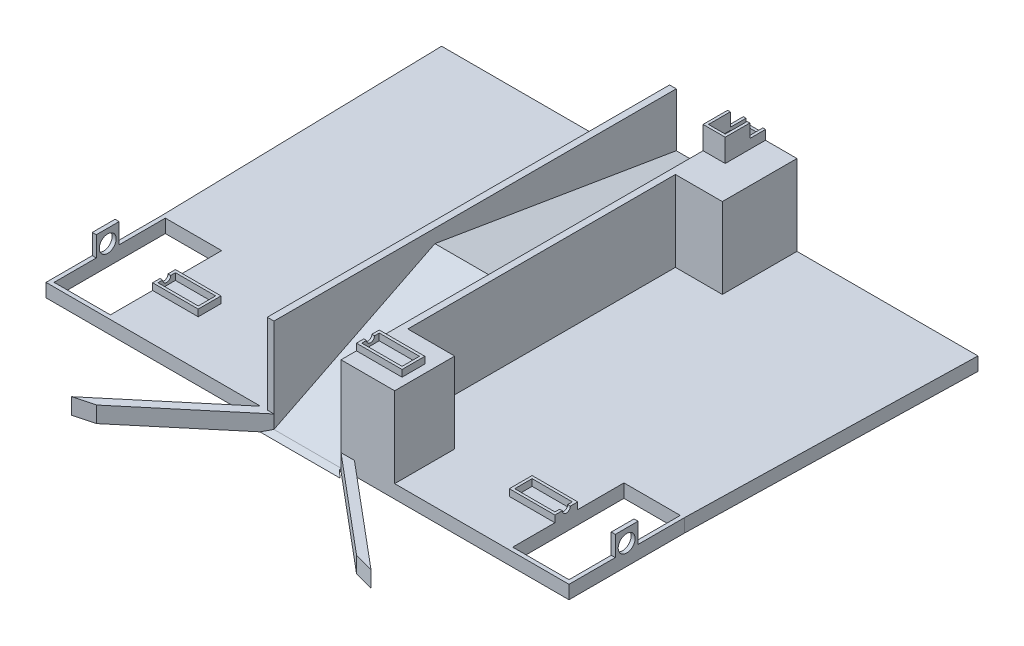
SolidWorks part; units mm, degrees
ref_plane "Front Plane" through (0, 0, 0) normal (0, 0, 1) x (1, 0, 0)
ref_plane "Top Plane" through (0, 0, 0) normal (0, 1, 0) x (1, 0, 0)
ref_plane "Right Plane" through (0, 0, 0) normal (1, 0, 0) x (0, 0, -1)
sketch "Sketch1" plane through (0, 0, 0) normal (0, 1, 0) x (1, 0, 0)
  line L1 (-100.4558, 255.2091) -> (299.5442, 255.2091)
  line L2 (-100.4558, 255.2091) -> (-95.4558, 41.2091)
  line L3 (-50.4558, -44.7909) -> (249.5442, -44.7909)
  line L5 (-95.4558, 41.2091) -> (-50.4558, 41.2091)
  line L8 (-50.4558, 41.2091) -> (-50.4558, -44.7909)
  line L23 (99.5442, 255.2091) -> (99.5442, -44.7909) construction
  line L32 (294.5442, 41.2091) -> (249.5442, 41.2091)
  line L33 (299.5442, 255.2091) -> (294.5442, 41.2091)
  line L34 (249.5442, 41.2091) -> (249.5442, -44.7909)
  point P32 (199.0884, -22.3492)
  dimension "D3" = 200
  dimension "D4" = 300
  dimension "D2" = 86
  dimension "D11" = 45
  dimension "D12" = 150
extrude "Boss-Extrude3" add sketch "Sketch1" along normal blind 10
sketch "Sketch2" plane through (0, 10, 0) normal (0, 1, 0) x (1, 0, 0)
  line L0 (-50.4558, 41.2091) -> (-50.4558, -44.7909) construction
  line L1 (-50.4558, 6.7091) -> (-16.4558, 6.7091)
  line L3 (-50.4558, 6.7091) -> (-50.4558, -10.2909)
  line L4 (-50.4558, -10.2909) -> (-16.4558, -10.2909)
  line L5 (-16.4558, 6.7091) -> (-16.4558, -10.2909)
  line L6 (-13, 6.7091) -> (-33.4558, -10.2909) construction
  line L7 (-48.4558, 4.7091) -> (-18.4558, 4.7091)
  line L8 (-48.4558, 4.7091) -> (-48.4558, -8.2909)
  line L9 (-48.4558, -8.2909) -> (-18.4558, -8.2909)
  line L10 (-18.4558, 4.7091) -> (-18.4558, -8.2909)
  line L11 (-16.4558, -1.7909) -> (-50.4558, -1.7909) construction
  line L12 (-50.4558, -44.7909) -> (249.5442, -44.7909) construction
  line L13 (99.5442, 255.2091) -> (99.5442, -44.7909) construction
  line L14 (299.5442, 255.2091) -> (-100.4558, 255.2091) construction
  line L15 (215.5442, -1.7909) -> (249.5442, -1.7909) construction
  line L16 (212.0884, 6.7091) -> (232.5442, -10.2909) construction
  line L17 (217.5442, 4.7091) -> (217.5442, -8.2909)
  line L18 (247.5442, -8.2909) -> (217.5442, -8.2909)
  line L19 (247.5442, 4.7091) -> (247.5442, -8.2909)
  line L20 (247.5442, 4.7091) -> (217.5442, 4.7091)
  line L21 (215.5442, 6.7091) -> (215.5442, -10.2909)
  line L22 (249.5442, -10.2909) -> (215.5442, -10.2909)
  line L23 (249.5442, 6.7091) -> (249.5442, -10.2909)
  line L24 (249.5442, 6.7091) -> (215.5442, 6.7091)
  dimension "D1" = 2
  dimension "D2" = 2
  dimension "D3" = 2
  dimension "D4" = 2
  dimension "D5" = 30
  dimension "D6" = 13
  dimension "D7" = 43
extrude "Boss-Extrude4" add sketch "Sketch2" along normal blind 5
sketch "Sketch3" plane through (0, 10, 0) normal (0, 1, 0) x (1, 0, 0)
  line L0 (99.5442, 255.2091) -> (99.5442, -44.7909) construction
  line L1 (299.5442, 255.2091) -> (-100.4558, 255.2091) construction
  line L2 (-50.4558, -44.7909) -> (249.5442, -44.7909) construction
  line L3 (74.5442, -44.7909) -> (74.5442, 75.2091)
  line L4 (74.5442, 75.2091) -> (124.5442, 75.2091)
  line L5 (124.5442, 75.2091) -> (124.5442, -44.7909)
  line L22 (215.5442, -10.2909) -> (215.5442, 6.7091)
  line L23 (215.5442, 6.7091) -> (249.5442, 6.7091)
  line L24 (249.5442, 6.7091) -> (249.5442, 41.2091)
  line L25 (249.5442, 41.2091) -> (294.5442, 41.2091)
  line L26 (294.5442, 41.2091) -> (299.5442, 255.2091)
  line L27 (299.5442, 255.2091) -> (-100.4558, 255.2091)
  line L28 (-100.4558, 255.2091) -> (-95.4558, 41.2091)
  line L29 (-95.4558, 41.2091) -> (-50.4558, 41.2091)
  line L30 (-50.4558, 41.2091) -> (-50.4558, 6.7091)
  line L31 (-50.4558, 6.7091) -> (-16.4558, 6.7091)
  line L32 (-16.4558, 6.7091) -> (-16.4558, -10.2909)
  line L33 (-16.4558, -10.2909) -> (-50.4558, -10.2909)
  line L34 (-50.4558, -10.2909) -> (-50.4558, -44.7909)
  line L35 (-50.4558, -44.7909) -> (249.5442, -44.7909)
  line L36 (249.5442, -44.7909) -> (249.5442, -10.2909)
  line L37 (249.5442, -10.2909) -> (215.5442, -10.2909)
  line L51 (74.5442, -44.7909) -> (124.5442, -44.7909)
  dimension "D1" = 50
  dimension "D2" = 25
  dimension "D3" = 120
extrude "Boss-Extrude5" add sketch "Sketch3" along normal blind 50
sketch "Sketch4" plane through (124.5442, 0, 0) normal (1, 0, 0) x (0, 0, -1)
  line L2 (-44.7909, 60) -> (75.2091, 60)
  line L3 (75.2091, 60) -> (-44.7909, 0)
  line L4 (-44.7909, 60) -> (-44.7909, 0)
extrude "Cut-Extrude2" cut sketch "Sketch4" against normal up to vertex (50 mm away) up to point (74.5442, 60, 44.7909)
sketch "Sketch5" plane through (0, 10, 0) normal (0, 1, 0) x (1, 0, 0)
  line L0 (74.5442, 75.2091) -> (74.5442, 255.2091)
  line L1 (299.5442, 255.2091) -> (-100.4558, 255.2091) construction
  line L2 (74.5442, 255.2091) -> (124.5442, 255.2091)
  line L3 (124.5442, 255.2091) -> (124.5442, 75.2091)
  line L4 (74.5442, 75.2091) -> (124.5442, 75.2091)
  line L5 (74.5442, 75.2091) -> (74.5442, -24.7909) construction
extrude "Boss-Extrude6" add sketch "Sketch5" along normal blind 50
sketch "Sketch6" plane through (124.5442, 0, 0) normal (1, 0, 0) x (0, 0, -1)
  line L2 (75.2091, 60) -> (255.2091, 60)
  line L3 (255.2091, 60) -> (255.2091, 30)
  line L4 (255.2091, 60) -> (255.2091, 10) construction
  line L5 (255.2091, 30) -> (75.2091, 60)
  dimension "D1" = 30
extrude "Cut-Extrude3" cut sketch "Sketch6" against normal through all contours L2 L3 L5
sketch "Sketch7" plane through (0, 0, 0) normal (0, 1, 0) x (1, 0, 0)
  line L0 (69.5442, 255.2091) -> (69.5442, -44.7909)
  line L1 (74.5442, 255.2091) -> (-100.4558, 255.2091) construction
  line L2 (-50.4558, -44.7909) -> (74.5442, -44.7909) construction
  line L3 (69.5442, -44.7909) -> (74.5442, -44.7909)
  line L4 (74.5442, -44.7909) -> (74.5442, 255.2091)
  line L5 (74.5442, 255.2091) -> (74.5442, -24.7909) construction
  line L6 (74.5442, 255.2091) -> (124.5442, 255.2091) construction
  line L7 (74.5442, 255.2091) -> (69.5442, 255.2091)
  line L8 (124.5442, 255.2091) -> (129.5442, 255.2091)
  line L9 (299.5442, 255.2091) -> (124.5442, 255.2091) construction
  line L10 (129.5442, 255.2091) -> (129.5442, -44.7909)
  line L11 (124.5442, -44.7909) -> (249.5442, -44.7909) construction
  line L12 (129.5442, -44.7909) -> (124.5442, -44.7909)
  line L13 (124.5442, -44.7909) -> (124.5442, 255.2091)
  line L14 (129.5442, -44.7909) -> (164.5442, -44.7909)
  line L15 (124.5442, -44.7909) -> (249.5442, -44.7909) construction
  line L16 (164.5442, -44.7909) -> (164.5442, 0)
  line L17 (164.5442, 0) -> (129.5442, 0)
  dimension "D1" = 5
  dimension "D2" = 5
  dimension "D3" = 35
extrude "Boss-Extrude7" add sketch "Sketch7" along normal blind 70 contours L16 L17 L10 L14 | L7 L0 L3 L4 | L13 L8 L10 L12 region at (147.0442, 0, 22.3954)
sketch "Sketch9" plane through (0, 70, 0) normal (0, 1, 0) x (1, 0, 0)
  line L0 (124.5442, -44.7909) -> (124.5442, 75.2091) construction
  line L1 (124.5442, -16.2909) -> (158.5442, -16.2909)
  line L2 (124.5442, -16.2909) -> (124.5442, -33.2909)
  line L3 (124.5442, -33.2909) -> (158.5442, -33.2909)
  line L4 (158.5442, -16.2909) -> (158.5442, -33.2909)
  line L5 (158.5442, -24.7909) -> (124.5442, -24.7909) construction
  line L6 (126.5442, -18.2909) -> (156.5442, -18.2909)
  line L7 (126.5442, -18.2909) -> (126.5442, -31.2909)
  line L8 (126.5442, -31.2909) -> (156.5442, -31.2909)
  line L9 (156.5442, -18.2909) -> (156.5442, -31.2909)
  line L10 (141.5442, -16.2909) -> (141.5442, -35.4954) construction
  line L11 (164.5442, -44.7909) -> (124.5442, -44.7909) construction
  dimension "D1" = 2
  dimension "D2" = 2
  dimension "D3" = 2
  dimension "D4" = 2
  dimension "D5" = 30
  dimension "D6" = 13
  dimension "D7" = 20
extrude "Boss-Extrude8" add sketch "Sketch9" along normal blind 5 contours L2 L1 L4 L3 | L7 L6 L9 L8
sketch "Sketch10" plane through (129.5442, 0, 0) normal (1, 0, 0) x (0, 0, -1)
  line L0 (199.5615, 70) -> (199.5615, 10)
  line L1 (255.2091, 70) -> (0, 70) construction
  line L2 (0, 10) -> (255.2091, 10) construction
  line L3 (199.5615, 10) -> (255.2091, 10)
  line L4 (255.2091, 10) -> (255.2091, 70)
  line L5 (255.2091, 70) -> (199.5615, 70)
extrude "Boss-Extrude9" add sketch "Sketch10" along normal blind 35
sketch "Sketch13" plane through (0, 70, 0) normal (0, 1, 0) x (1, 0, 0)
  line L0 (141.0442, 225.2091) -> (124.5442, 225.2091)
  line L2 (124.5442, 225.2091) -> (124.5442, 255.2091)
  line L3 (124.5442, 255.2091) -> (141.0442, 255.2091)
  line L4 (141.0442, 255.2091) -> (141.0442, 225.2091)
  line L5 (139.0442, 227.2091) -> (126.5442, 227.2091)
  line L6 (126.5442, 227.2091) -> (126.5442, 253.2091)
  line L7 (126.5442, 253.2091) -> (139.0442, 253.2091)
  line L8 (139.0442, 253.2091) -> (139.0442, 227.2091)
  line L15 (124.5442, 255.2091) -> (164.5442, 255.2091) construction
  point P2 (126.7166, 255.2091)
  point P8 (141.5391, 254.8671)
  point P12 (135.5412, 253.2055)
  point P13 (137.5482, 231.331)
  point P14 (0, 0)
  point P16 (141.0442, 231.7091)
  dimension "D2" = 16.5
  dimension "D3" = 30
  dimension "D4" = 2
  dimension "D5" = 2
  dimension "D6" = 2
  dimension "D7" = 2
extrude "Boss-Extrude11" add sketch "Sketch13" along normal blind 7
sketch "Sketch14" plane through (0, 0, 0) normal (0, -1, 0) x (1, 0, 0)
  line L0 (294.5442, -41.2091) -> (299.5442, -255.2091) construction
  line L1 (299.5442, -255.2091) -> (-100.4558, -255.2091) construction
  circle A0 centre (284.1896, -240.2091) radius 8
  dimension "D1" = 15
  dimension "D2" = 15
sketch "Sketch16" plane through (0, 0, 0) normal (0, -1, 0) x (1, 0, 0)
  line L0 (-100.4558, -255.2091) -> (-95.4558, -41.2091) construction
  line L1 (299.5442, -255.2091) -> (-100.4558, -255.2091) construction
  circle A0 centre (-85.1012, -240.2091) radius 8
  dimension "D1" = 15
  dimension "D2" = 15
sketch "Sketch19" plane through (0, 0, 44.7909) normal (0, 0, 1) x (1, 0, 0)
  line L0 (-50.4558, 10) -> (69.5442, 10) construction
  line L1 (74.5442, 0) -> (64.5442, 0)
  line L2 (74.5442, 0) -> (74.5442, 10)
  line L3 (74.5442, 10) -> (64.5442, 10)
  line L4 (64.5442, 0) -> (64.5442, 10)
  line L6 (124.5442, 0) -> (134.5442, 0)
  line L7 (124.5442, 0) -> (124.5442, 10)
  line L8 (124.5442, 10) -> (134.5442, 10)
  line L9 (134.5442, 0) -> (134.5442, 10)
  point P12 (0, 0)
  dimension "D1" = 10
  dimension "D2" = 10
  dimension "D3" = 10
sketch "Sketch20" plane through (0, 0, 0) normal (0, 1, 0) x (1, 0, 0)
  line L0 (64.5442, -44.7909) -> (-12.0602, -109.0696)
  line L1 (74.5442, -44.7909) -> (64.5442, -44.7909) construction
  line L2 (74.5442, -44.7909) -> (2.6312, -105.1331)
  line L3 (74.5442, -44.7909) -> (64.5442, -44.7909) construction
  line L4 (-50.4558, -44.7909) -> (69.5442, -44.7909) construction
  line L5 (124.5442, -44.7909) -> (196.4572, -105.1331)
  line L6 (134.5442, -44.7909) -> (211.1486, -109.0696)
  line L7 (124.5442, -44.7909) -> (134.5442, -44.7909) construction
  line L8 (164.5442, -44.7909) -> (124.5442, -44.7909) construction
  line L9 (196.4572, -105.1331) -> (211.1486, -109.0696)
  line L10 (2.6312, -105.1331) -> (-12.0602, -109.0696)
  line L11 (64.5442, -44.7909) -> (74.5442, -44.7909)
  line L12 (124.5442, -44.7909) -> (134.5442, -44.7909)
  dimension "D1" = 40
  dimension "D2" = 40
  dimension "D3" = 25
  dimension "D4" = 25
  dimension "D5" = 100
  dimension "D6" = 100
  dimension "D7" = 10
  dimension "D8" = 10
extrude "Boss-Extrude16" add sketch "Sketch20" along normal blind 10 and the other way blind 2
sketch "Sketch21" plane through (0, 0, 0) normal (0, -1, 0) x (1, 0, 0)
  line L0 (74.5442, 44.7909) -> (124.5442, 44.7909) construction
  line L1 (74.5442, 44.6775) -> (124.5442, 44.6775)
  line L2 (74.5442, 44.6775) -> (74.5442, 14.7909)
  line L3 (74.5442, 14.7909) -> (124.5442, 14.7909)
  line L4 (124.5442, 44.6775) -> (124.5442, 14.7909)
  dimension "D1" = 50
  dimension "D2" = 30
extrude "Boss-Extrude19" add sketch "Sketch21" along normal blind 2
sketch "Sketch23" plane through (124.5442, 0, 0) normal (1, 0, 0) x (0, 0, -1)
  line L0 (-44.7909, 0) -> (-49.5909, -2)
  line L1 (-109.0696, -2) -> (-44.7909, -2) construction
  line L2 (-49.5909, -2) -> (-44.6775, -2)
  line L3 (-44.6775, -2) -> (-49.5909, -2)
  line L5 (-44.7909, 0) -> (-44.6775, -2)
  point P5 (-44.7909, -25)
  dimension "D1" = 22.62
sketch "Sketch24" plane through (0, 0, 44.7909) normal (0, 0, -1) x (-1, 0, 0)
  line L1 (-74.5442, 0) -> (-64.5442, 0)
  line L2 (-74.5442, 0) -> (-74.5442, -2)
  line L3 (-74.5442, -2) -> (-64.5442, -2)
  line L4 (-64.5442, 0) -> (-64.5442, -2)
  line L5 (-134.5442, 0) -> (-124.5442, 0)
  line L6 (-134.5442, 0) -> (-134.5442, -2)
  line L7 (-134.5442, -2) -> (-124.5442, -2)
  line L8 (-124.5442, 0) -> (-124.5442, -2)
extrude "Boss-Extrude20" add sketch "Sketch24" along normal blind 30
extrude "Boss-Extrude23" add sketch "Sketch23" along normal offset from surface 1 and the other way up to surface separate body contours L5 L0 L2 region at (124.5442, -1.3333, 46.3531) up to face at (153.3094, 3.2, 68.9277) other way up to face at (45.779, 3.2, 68.9277)
sketch "Sketch28" plane through (0, 0, -41.2091) normal (0, 0, 1) x (1, 0, 0)
  line L0 (-95.4558, 0) -> (-50.4558, 0) construction
  line L1 (-95.4558, 10) -> (-92.4558, 10)
  line L2 (-95.4558, 10) -> (-95.4558, 0)
  line L3 (-95.4558, 0) -> (-92.4558, 0)
  line L4 (-92.4558, 10) -> (-92.4558, 0)
  dimension "D1" = 3
extrude "Boss-Extrude24" add sketch "Sketch28" along normal up to vertex (86 mm away) up to point (-50.4558, 0, 44.7909)
sketch "Sketch29" plane through (-50.4558, 0, 0) normal (-1, 0, 0) x (0, 0, 1)
  line L0 (14.7909, 0) -> (44.7909, 0) construction
  line L1 (44.7909, 10) -> (41.7909, 10)
  line L2 (44.7909, 10) -> (44.7909, 0)
  line L3 (44.7909, 0) -> (41.7909, 0)
  line L4 (41.7909, 10) -> (41.7909, 0)
  point P7 (0, 0)
  dimension "D1" = 3
extrude "Boss-Extrude25" add sketch "Sketch29" along normal up to next
sketch "Sketch30" plane through (0, 0, -41.2091) normal (0, 0, 1) x (1, 0, 0)
  line L0 (249.5442, 0) -> (294.5442, 0) construction
  line L1 (294.5442, 10) -> (291.5442, 10)
  line L2 (294.5442, 10) -> (294.5442, 0)
  line L3 (294.5442, 0) -> (291.5442, 0)
  line L4 (291.5442, 10) -> (291.5442, 0)
  dimension "D1" = 3
extrude "Boss-Extrude26" add sketch "Sketch30" along normal up to vertex (86 mm away) up to point (249.5442, 0, 44.7909)
sketch "Sketch31" plane through (249.5442, 0, 0) normal (1, 0, 0) x (0, 0, -1)
  line L0 (-14.7909, 0) -> (-44.7909, 0) construction
  line L1 (-44.7909, 10) -> (-41.7909, 10)
  line L2 (-44.7909, 10) -> (-44.7909, 0)
  line L3 (-44.7909, 0) -> (-41.7909, 0)
  line L4 (-41.7909, 10) -> (-41.7909, 0)
  dimension "D1" = 3
extrude "Boss-Extrude27" add sketch "Sketch31" along normal up to next
sketch "Sketch32" plane through (0, 70, 0) normal (0, 1, 0) x (1, 0, 0)
  line L0 (126.5442, 253.2091) -> (126.5442, 227.2091) construction
  line L1 (139.0442, 227.2091) -> (126.5442, 227.2091)
  line L2 (139.0442, 227.2091) -> (139.0442, 243.5091)
  line L3 (139.0442, 243.5091) -> (126.5442, 243.5091)
  line L4 (126.5442, 227.2091) -> (126.5442, 243.5091)
  dimension "D1" = 16.3
extrude "Boss-Extrude28" add sketch "Sketch32" along normal blind 5
sketch "Sketch34" plane through (0, 77, 0) normal (0, 1, 0) x (1, 0, 0)
  line L0 (126.5442, 243.5091) -> (124.5442, 243.5091)
  line L1 (124.5442, 255.2091) -> (124.5442, 225.2091) construction
  line L2 (124.5442, 243.5091) -> (124.5442, 225.2091)
  line L3 (124.5442, 225.2091) -> (141.0442, 225.2091)
  line L4 (124.5442, 225.2091) -> (141.0442, 225.2091) construction
  line L5 (141.0442, 225.2091) -> (141.0442, 243.5091)
  line L6 (141.0442, 225.2091) -> (141.0442, 255.2091) construction
  line L7 (141.0442, 243.5091) -> (139.0442, 243.5091)
  line L8 (139.0442, 243.5091) -> (139.0442, 227.2091)
  line L9 (139.0442, 227.2091) -> (126.5442, 227.2091)
  line L10 (126.5442, 227.2091) -> (126.5442, 243.5091)
  point P5 (141.0442, 231.7091)
extrude "Boss-Extrude31" add sketch "Sketch34" along normal blind 10
sketch "Sketch35" plane through (0, 0, -255.2091) normal (0, 0, -1) x (-1, 0, 0)
  line L0 (-139.0442, 77) -> (-139.0442, 74)
  line L1 (-141.0442, 77) -> (-124.5442, 77) construction
  line L2 (-139.0442, 74) -> (-126.5442, 74)
  line L3 (-126.5442, 74) -> (-126.5442, 77)
  line L4 (-141.0442, 77) -> (-141.0442, 70) construction
  line L5 (-124.5442, 77) -> (-124.5442, 30) construction
  line L6 (-139.0442, 77) -> (-126.5442, 77)
  dimension "D1" = 2
  dimension "D2" = 2
  dimension "D3" = 3
extrude "Cut-Extrude4" cut sketch "Sketch35" against normal up to next (2 mm away)
sketch "Sketch36" plane through (249.5442, 0, 0) normal (1, 0, 0) x (0, 0, -1)
  line L0 (-10.2909, 15) -> (6.7091, 15) construction
  arc A0 (1.2091, 15) -> (-4.7909, 15) centre (-1.7909, 15) cw
  point P5 (0, 15)
  dimension "D1" = 3
extrude "Cut-Extrude5" cut sketch "Sketch36" against normal blind 2 and the other way through all flip side to cut
sketch "Sketch37" plane through (-50.4558, 0, 0) normal (-1, 0, 0) x (0, 0, 1)
  line L0 (-6.7091, 15) -> (10.2909, 15) construction
  arc A0 (-1.2091, 15) -> (4.7909, 15) centre (1.7909, 15) ccw
  point P5 (0, 15)
  dimension "D1" = 3
extrude "Cut-Extrude6" cut sketch "Sketch37" against normal blind 2 and the other way through all
sketch "Sketch38" plane through (124.5442, 0, 0) normal (-1, 0, 0) x (0, 0, 1)
  line L0 (16.2909, 75) -> (33.2909, 75) construction
  line L1 (21.7909, 75) -> (27.7909, 75)
  arc A0 (27.7909, 75) -> (21.7909, 75) centre (24.7909, 75) cw
  dimension "D1" = 3
extrude "Cut-Extrude9" cut sketch "Sketch38" against normal blind 2
sketch "Sketch39" plane through (0, 10, 0) normal (0, 1, 0) x (1, 0, 0)
  line L0 (291.5442, 6.7091) -> (294.5442, 6.7091)
  line L1 (291.5442, -41.7909) -> (291.5442, 41.2091) construction
  line L2 (294.5442, 6.7091) -> (294.5442, -10.2909)
  line L3 (294.5442, -10.2909) -> (291.5442, -10.2909)
  line L4 (291.5442, 6.7091) -> (291.5442, -10.2909)
  line L5 (249.5442, 6.7091) -> (291.5442, 6.7091) construction
  line L6 (249.5442, -10.2909) -> (291.5442, -10.2909) construction
  line L7 (294.5442, -44.7909) -> (294.5442, 41.2091) construction
  point P9 (0, 0)
  point P11 (0, 0)
extrude "Boss-Extrude32" add sketch "Sketch39" along normal blind 15
sketch "Sketch40" plane through (294.5442, 0, 0) normal (1, 0, 0) x (0, 0, -1)
  line L0 (-1.7909, 25) -> (-1.7909, 0) construction
  line L1 (-10.2909, 25) -> (6.7091, 25) construction
  line L2 (-44.7909, 0) -> (41.2091, 0) construction
  line L3 (-10.2909, 15) -> (6.7091, 15) construction
  line L4 (-10.2909, 25) -> (-10.2909, 10) construction
  line L5 (6.7091, 25) -> (6.7091, 10) construction
  line L6 (0, 10) -> (-44.7909, 10) construction
  circle A0 centre (-1.7909, 15) radius 6.3
  dimension "D2" = 12.6
  dimension "D1" = 5
extrude "Cut-Extrude10" cut sketch "Sketch40" against normal up to next (3 mm away)
sketch "Sketch41" plane through (0, 10, 0) normal (0, 1, 0) x (1, 0, 0)
  line L0 (-95.4558, 6.7091) -> (-92.4558, 6.7091)
  line L1 (-95.4558, -44.7909) -> (-95.4558, 41.2091) construction
  line L2 (-92.4558, -41.7909) -> (-92.4558, 41.2091) construction
  line L3 (-92.4558, 6.7091) -> (-92.4558, -10.2909)
  line L4 (-92.4558, -10.2909) -> (-95.4558, -10.2909)
  line L5 (-95.4558, -10.2909) -> (-95.4558, 6.7091)
  line L6 (-92.4558, 6.7091) -> (-50.4558, 6.7091) construction
  line L7 (-92.4558, -10.2909) -> (-50.4558, -10.2909) construction
extrude "Boss-Extrude33" add sketch "Sketch41" along normal blind 15
sketch "Sketch42" plane through (-95.4558, 0, 0) normal (-1, 0, 0) x (0, 0, 1)
  line L0 (1.7909, 25) -> (1.7909, 0) construction
  line L1 (-6.7091, 25) -> (10.2909, 25) construction
  line L2 (44.7909, 0) -> (-41.2091, 0) construction
  line L3 (-6.7091, 15) -> (10.2909, 15) construction
  line L4 (10.2909, 25) -> (10.2909, 10) construction
  line L5 (44.7909, 10) -> (-255.2091, 10) construction
  circle A0 centre (1.7909, 15) radius 6.3
  point P14 (3.908, 15)
  dimension "D2" = 12.6
  dimension "D1" = 5
extrude "Cut-Extrude11" cut sketch "Sketch42" against normal up to next (3 mm away)
extrude "Boss-Extrude34" add sketch "Sketch14" along normal blind 5
extrude "Boss-Extrude35" add sketch "Sketch16" along normal blind 5
equation "\"draggingScrewDiameter\"= 2"
equation "\"chassisWidth\"= 400"
equation "\"D3@Sketch1\"=0.5 * \"chassisWidth\""
equation "\"chassisLength\"=300"
equation "\"D4@Sketch1\"=\"chassisLength\""
equation "\"wheelDepth\" = 86"
equation "\"D2@Sketch1\"=\"wheelDepth\""
equation "\"wheelWidth\" = 50"
equation "\"D12@Sketch1\"=(0.5 * \"chassisWidth\") - \"wheelWidth\""
equation "\"baseThickness\"=10"
equation "\"D1@Boss-Extrude3\"=\"baseThickness\""
equation "\"D7@Sketch2\"=\"wheelDepth\" * 0.5"
equation "\"rampLength\"=120"
equation "\"D3@Sketch3\"=\"rampLength\""
equation "\"rampHeight\"=50"
equation "\"D1@Boss-Extrude5\"=\"rampHeight\""
equation "\"D1@Boss-Extrude6\"=\"rampHeight\""
equation "\"dumpHeight\"=30"
equation "\"D1@Sketch6\"=\"dumpHeight\""
equation "\"D1@Sketch23\"=atn( \"rampHeight\"/\"rampLength\")"
